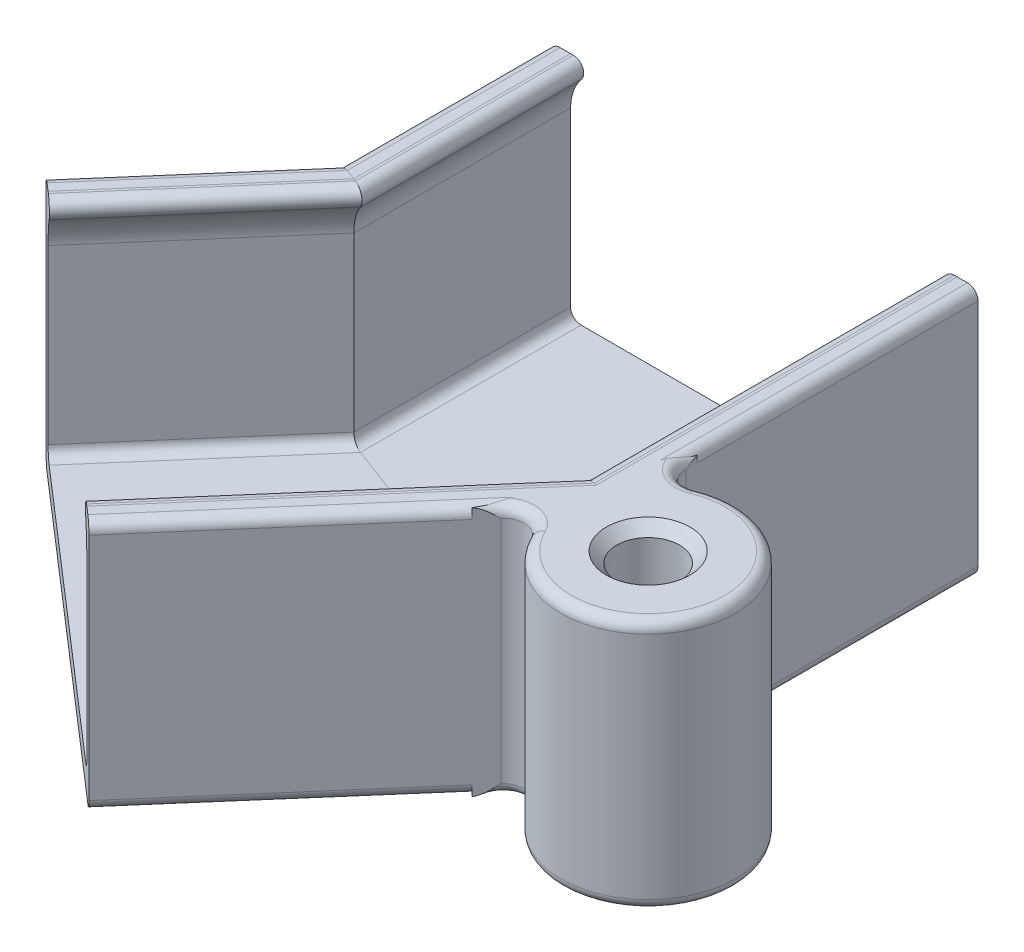
SolidWorks part; units mm, degrees
material "Maple"
ref_plane "Wasteboard" through (0, 0, 0) normal (0, 0, 1) x (1, 0, 0)
ref_plane "Left-Right" through (0, 0, 0) normal (0, 1, 0) x (1, 0, 0)
ref_plane "Front-Back" through (0, 0, 0) normal (1, 0, 0) x (0, 0, -1)
sketch "Sketch1" plane through (0, 0, 0) normal (0, 0, 1) x (1, 0, 0)
  line L0 (-17.5, -12.023) -> (17.5, -12.023)
  line L1 (18.5, -11.023) -> (18.5, 5.477)
  line L2 (18.5, 9.977) -> (19.5, 9.977)
  line L3 (20.5, 8.977) -> (20.5, -13.023)
  line L4 (19.5, -14.023) -> (-19.5, -14.023)
  line L5 (18.2426, 9.977) -> (7.9275, 9.977) construction
  line L6 (0, -8.9794) -> (0, 8.6415) construction
  line L7 (18.5, 9.977) -> (18.2426, 9.977)
  line L8 (-18.2426, 9.977) -> (-7.9275, 9.977) construction
  line L9 (-18.5, 9.977) -> (-18.2426, 9.977)
  line L10 (-20.5, 8.977) -> (-20.5, -13.023)
  line L11 (-18.5, 9.977) -> (-19.5, 9.977)
  line L12 (-18.5, -11.023) -> (-18.5, 5.477)
  arc A0 (18.5, 5.477) -> (17.4713, 8.3406) centre (14, 5.477) ccw
  arc A1 (18.2426, 9.977) -> (17.4713, 8.3406) centre (18.2426, 8.977) ccw
  arc A2 (19.5, 9.977) -> (20.5, 8.977) centre (19.5, 8.977) cw
  arc A3 (17.5, -12.023) -> (18.5, -11.023) centre (17.5, -11.023) ccw
  arc A4 (20.5, -13.023) -> (19.5, -14.023) centre (19.5, -13.023) cw
  arc A5 (-20.5, -13.023) -> (-19.5, -14.023) centre (-19.5, -13.023) ccw
  arc A6 (-17.5, -12.023) -> (-18.5, -11.023) centre (-17.5, -11.023) cw
  arc A7 (-19.5, 9.977) -> (-20.5, 8.977) centre (-19.5, 8.977) ccw
  arc A8 (-18.2426, 9.977) -> (-17.4713, 8.3406) centre (-18.2426, 8.977) cw
  arc A9 (-18.5, 5.477) -> (-17.4713, 8.3406) centre (-14, 5.477) cw
  point P0 (-20.5, -14.023)
  point P6 (0, -12.023)
  point P8 (14, 9.977)
  point P14 (18.5, 5.477)
  point P23 (20.5, -14.023)
  point P40 (0, -14.023)
  point P41 (-14, 9.977)
  point P42 (0, 0)
  dimension "D2" = 9
  dimension "D6" = 1
  dimension "D7" = 1
  dimension "D1" = 20.5
  dimension "D3" = 2
  dimension "D4" = 2
  dimension "D5" = 22
sketch "Sketch3" plane through (0, 0, 0) normal (0, 1, 0) x (1, 0, 0)
  line L0 (0, 0) -> (0, -27.6514)
  line L1 (0, -27.6514) -> (-18.1174, -48.5407)
  line L2 (-20.5, -20) -> (0, -20) construction
  line L3 (-5.0133, -33.4317) -> (-20.5, -20) construction
  point P5 (0, 0)
  point P8 (0, 0)
  point P9 (-17.709, -33.8624)
  point P10 (0, 0)
  dimension "D1" = 20
  dimension "D2" = 40.935
  dimension "D3" = 0
sweep "Sweep1" add profiles "Sketch1" path "Sketch3"
ref_plane "Plane2" through (0, -14.023, 0) normal (0, -1, 0) x (-1, 0, 0)
sketch "Sketch4" plane through (0, -14.023, 0) normal (0, -1, 0) x (-1, 0, 0)
  line L0 (-19.5, -34.9297) -> (-37.0585, -41.4832) construction
  line L1 (-19.5, -34.9297) -> (19.5, -20.3732) construction
  line L2 (-20.5, -27.9661) -> (-20.5, -26.9084)
  line L3 (-21.5517, -41.5661) -> (-20.5, -35.3029) construction
  line L4 (-20.5, -35.3029) -> (-25.3982, -31.2605) construction
  line L5 (-25.3982, -31.2605) -> (-31.3481, -33.4813) construction
  line L6 (-31.3481, -33.4813) -> (-32.3998, -39.7444) construction
  line L7 (-32.3998, -39.7444) -> (-27.5017, -43.7868) construction
  line L8 (-27.5017, -43.7868) -> (-21.5517, -41.5661) construction
  line L9 (-20.5, 0) -> (-20.5, -35.3029) construction
  line L10 (-20.5, -26.9084) -> (-19.5, -29.4364)
  line L11 (-20.5, -35.3029) -> (2.6307, -61.9725) construction
  line L12 (-14.395, -42.3419) -> (-15.6929, -40.8455)
  line L13 (-19.5, -29.4364) -> (-19.5, -34.9297)
  line L14 (-19.5, -34.9297) -> (-15.505, -39.5359)
  line L15 (-19.5, -34.9297) -> (3.3861, -61.3173) construction
  line L16 (-15.505, -39.5359) -> (-14.395, -42.3419)
  circle A0 centre (-26.4499, -37.5237) radius 3
  circle A1 centre (-26.4499, -37.5237) radius 5.5 construction
  arc A2 (-23.2639, -29.8145) -> (-18.9919, -41.2601) centre (-26.4499, -37.5237) ccw
  arc A3 (-15.6929, -40.8455) -> (-18.9919, -41.2601) centre (-17.2038, -42.1559) ccw
  arc A4 (-20.5, -27.9661) -> (-23.2639, -29.8145) centre (-22.5, -27.9661) cw
  point P8 (-32.7412, -32.0462)
  point P30 (-18.1244, -38.0419)
  point P33 (-14.5563, -42.1559)
  point P34 (-15.3241, -39.7444)
  point P35 (-20.5, -26.9084)
  dimension "D1" = 11
  dimension "D2" = 2
  dimension "D3" = 2
extrude "Boss-Extrude2" add sketch "Sketch4" against normal through all
sketch "Sketch5" plane through (0, -14.023, 0) normal (0, -1, 0) x (-1, 0, 0)
  line L0 (-19.5, -34.9297) -> (-26.4499, -37.5237)
  line L3 (-27.5017, -43.7868) -> (-21.5517, -41.5661)
  line L4 (-21.5517, -41.5661) -> (-20.5, -35.3029)
  line L5 (-20.5, -35.3029) -> (-25.3982, -31.2605)
  line L6 (-25.3982, -31.2605) -> (-31.3481, -33.4813)
  line L7 (-31.3481, -33.4813) -> (-32.3998, -39.7444)
  line L8 (-32.3998, -39.7444) -> (-27.5017, -43.7868)
  circle A0 centre (-26.4499, -37.5237) radius 5.5 construction
  point P3 (-21.0259, -38.4345)
  point P4 (-20.1127, -37.9398)
  dimension "D1" = 11
extrude "Cut-Extrude2" cut sketch "Sketch5" against normal blind 6 draft 2
chamfer "Chamfer1" distance 1 angle 45 6 edges at (28.2999, -8.023, 32.5672) (23.0825, -8.023, 33.4433) (21.2325, -8.023, 38.3998) (24.6, -8.023, 42.4801) (29.8174, -8.023, 41.604) (31.6673, -8.023, 36.6475)
fillet "Fillet2" radius 1 3 edges at (21.3882, 9.977, 29.6286) (17.4531, 9.977, 40.1715) (34.2649, 9.977, 40.4405)
fillet "Fillet3" radius 1 3 edges at (21.3882, -14.023, 29.6286) (17.4531, -14.023, 40.1715) (34.2649, -14.023, 40.4405)
chamfer "Chamfer2" distance 1 angle 45 1 edges at (26.4499, 9.977, 34.5237)
